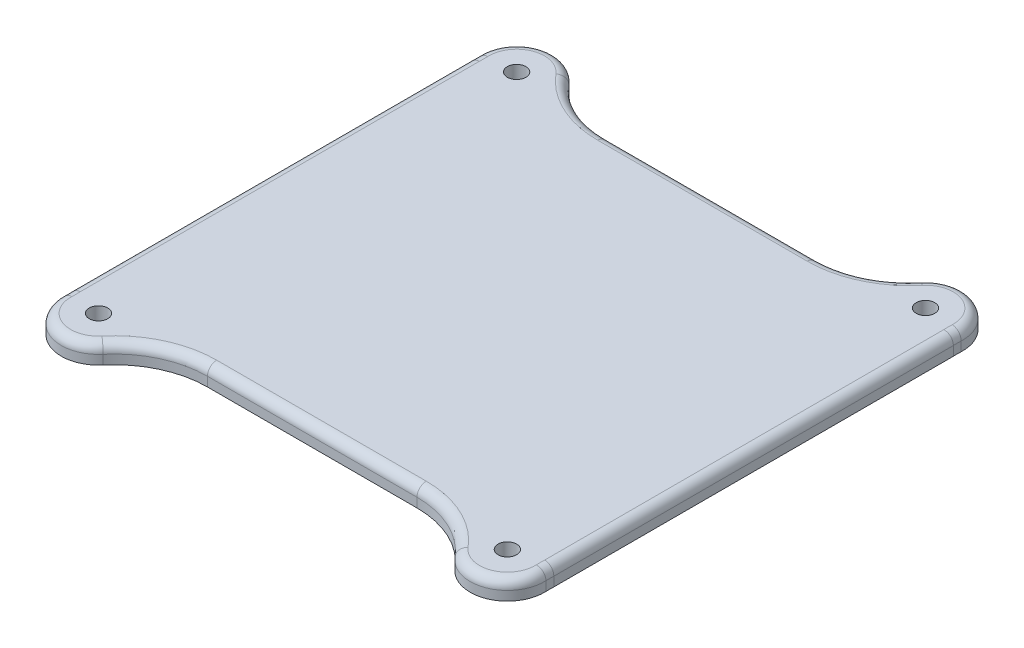
SolidWorks part; units mm, degrees
ref_plane "Front Plane" through (0, 0, 0) normal (0, 0, 1) x (1, 0, 0)
ref_plane "Top Plane" through (0, 0, 0) normal (0, 1, 0) x (1, 0, 0)
ref_plane "Right Plane" through (0, 0, 0) normal (1, 0, 0) x (0, 0, -1)
sketch "Sketch1" plane through (0, 20, 0) normal (0, 1, 0) x (1, 0, 0)
  line L4 (11.2762, 21.5) -> (-11.2762, 21.5)
  line L5 (-26, 21.5) -> (-26, -21.5)
  line L6 (-11.2762, -21.5) -> (11.2762, -21.5)
  line L7 (26, -21.5) -> (26, 21.5)
  line L8 (11.2762, 21.5) -> (-11.2762, 21.5)
  line L9 (-26, 21.5) -> (-26, -21.5)
  line L10 (-11.2762, -21.5) -> (11.2762, -21.5)
  line L11 (26, -21.5) -> (26, 21.5)
  circle A0 centre (-22, -22.5) radius 1 construction
  circle A1 centre (22, -22.5) radius 1 construction
  circle A2 centre (22, 22.5) radius 1 construction
  circle A3 centre (-22, 22.5) radius 1 construction
  circle A4 centre (-22, -22.5) radius 1
  circle A5 centre (22, -22.5) radius 1
  circle A6 centre (22, 22.5) radius 1
  circle A7 centre (-22, 22.5) radius 1
  arc A12 (-18.9361, 25.0714) -> (-11.2762, 21.5) centre (-11.2762, 31.5) ccw
  arc A13 (-18.9361, 25.0714) -> (-25.997, 22.3451) centre (-22, 22.5) ccw
  arc A14 (-26, 21.5) -> (-25.997, 22.3451) centre (-35.9895, 21.958) ccw
  arc A15 (-25.997, -22.3451) -> (-26, -21.5) centre (-35.9895, -21.958) ccw
  arc A16 (-25.997, -22.3451) -> (-18.9361, -25.0714) centre (-22, -22.5) ccw
  arc A17 (-11.2762, -21.5) -> (-18.9361, -25.0714) centre (-11.2762, -31.5) ccw
  arc A18 (18.9361, -25.0714) -> (11.2762, -21.5) centre (11.2762, -31.5) ccw
  arc A19 (18.9361, -25.0714) -> (25.997, -22.3451) centre (22, -22.5) ccw
  arc A20 (26, -21.5) -> (25.997, -22.3451) centre (35.9895, -21.958) ccw
  arc A21 (25.997, 22.3451) -> (26, 21.5) centre (35.9895, 21.958) ccw
  arc A22 (25.997, 22.3451) -> (18.9361, 25.0714) centre (22, 22.5) ccw
  arc A23 (11.2762, 21.5) -> (18.9361, 25.0714) centre (11.2762, 31.5) ccw
  arc A24 (-18.9361, 25.0714) -> (-11.2762, 21.5) centre (-11.2762, 31.5) ccw
  arc A25 (-18.9361, 25.0714) -> (-25.997, 22.3451) centre (-22, 22.5) ccw
  arc A26 (-26, 21.5) -> (-25.997, 22.3451) centre (-35.9895, 21.958) ccw
  arc A27 (-25.997, -22.3451) -> (-26, -21.5) centre (-35.9895, -21.958) ccw
  arc A28 (-25.997, -22.3451) -> (-18.9361, -25.0714) centre (-22, -22.5) ccw
  arc A29 (-11.2762, -21.5) -> (-18.9361, -25.0714) centre (-11.2762, -31.5) ccw
  arc A30 (18.9361, -25.0714) -> (11.2762, -21.5) centre (11.2762, -31.5) ccw
  arc A31 (18.9361, -25.0714) -> (25.997, -22.3451) centre (22, -22.5) ccw
  arc A32 (26, -21.5) -> (25.997, -22.3451) centre (35.9895, -21.958) ccw
  arc A33 (25.997, 22.3451) -> (26, 21.5) centre (35.9895, 21.958) ccw
  arc A34 (25.997, 22.3451) -> (18.9361, 25.0714) centre (22, 22.5) ccw
  arc A35 (11.2762, 21.5) -> (18.9361, 25.0714) centre (11.2762, 31.5) ccw
  dimension "D1" = 0
extrude "Boss-Extrude1" add sketch "Sketch1" along normal blind 2
fillet "Fillet1" radius 1 16 edges at (25.9896, 22, -21.9225) (23.4408, 22, -26.2315) (15.502, 22, -22.4367) (-25.9896, 22, -21.9225) (-23.4408, 22, -26.2315) (-15.502, 22, -22.4367) (-25.9896, 22, 21.9225) (-23.4408, 22, 26.2315) (-15.502, 22, 22.4367) (25.9896, 22, 21.9225) (23.4408, 22, 26.2315) (15.502, 22, 22.4367) (26, 22, 0) (-26, 22, 0) (0, 22, -21.5) (0, 22, 21.5)
